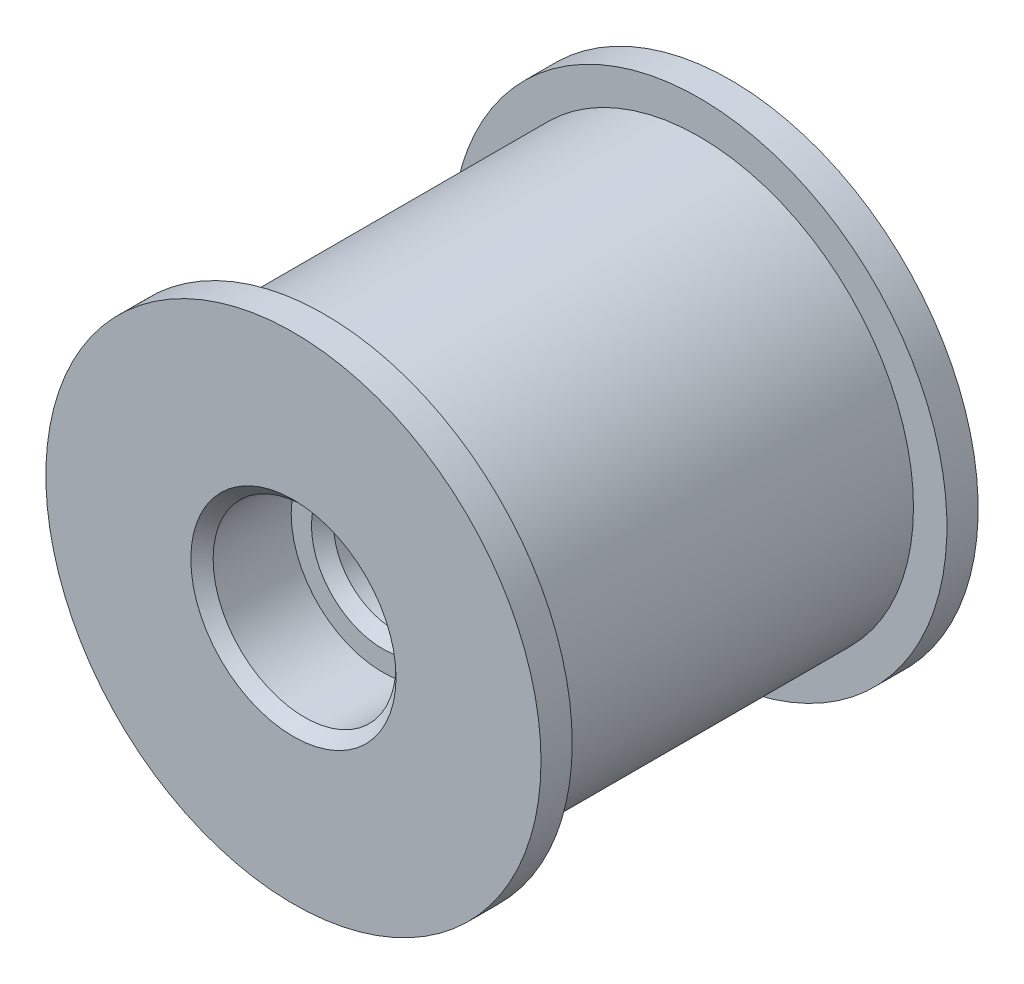
SolidWorks part; units mm, degrees
ref_plane "Ebene vorne" through (0, 0, 0) normal (0, 0, 1) x (1, 0, 0)
ref_plane "Ebene oben" through (0, 0, 0) normal (0, 1, 0) x (1, 0, 0)
ref_plane "Ebene rechts" through (0, 0, 0) normal (1, 0, 0) x (0, 0, -1)
sketch "Skizze1" plane through (0, 0, 0) normal (0, 0, 1) x (1, 0, 0)
  circle A0 centre (0, 0) radius 9.6
  dimension "D1" = 19.2
extrude "Aufsatz-Linear austragen1" add sketch "Skizze1" along normal blind 9.8 and the other way blind 9.8
ref_axis "Rotationsachse" [suppressed] through (0, 0, -9.8) along (0, 0, 1)
sketch "Skizze2" plane through (0, 0, 9.8) normal (0, 0, 1) x (1, 0, 0)
  circle A0 centre (0, 0) radius 11.1
  dimension "D1" = 22.2
extrude "Aufsatz-Linear austragen2" add sketch "Skizze2" against normal blind 1.4
sketch "Skizze3" plane through (0, 0, -9.8) normal (0, 0, -1) x (-1, 0, 0)
  circle A0 centre (0, 0) radius 11.1
  dimension "D1" = 22.2
extrude "Aufsatz-Linear austragen3" add sketch "Skizze3" against normal blind 1.4
sketch "Skizze8" plane through (0, 0, 0) normal (1, 0, 0) x (0, 0, -1)
  line L0 (9.8, 0) -> (9.8, 8)
  line L1 (9.8, -11.1) -> (9.8, 11.1) construction
  line L2 (9.8, 8) -> (8.4, 8)
  line L3 (8.4, 11.1) -> (8.4, -11.1) construction
  line L8 (8.4, 8) -> (-2.2, 4)
  line L9 (-2.2, 4) -> (-2.2, 2.691)
  line L10 (-2.2, 2.691) -> (-5.8, 2.691)
  line L11 (-5.8, 2.691) -> (-5.8, 4.1)
  line L12 (-5.8, 4.1) -> (-9.8, 4.1)
  line L13 (-9.8, 11.1) -> (-9.8, -11.1) construction
  line L14 (-9.8, 4.1) -> (-9.8, 0)
  line L15 (-9.8, 0) -> (9.8, 0)
  dimension "D1" = 8
  dimension "D2" = 4
  dimension "D3" = 4.1
  dimension "D4" = 12
  dimension "D5" = 4
revolve "Schnitt-Rotation1" cut sketch "Skizze8" angle 360 about axis through (0, 0, -9.8) along (0, 0, 1)
chamfer "Fase1" distance 0.5 3 edges at (-2.691, 0, 5.8) (-2.691, 0, 2.2) (-4.1, 0, 9.8)
